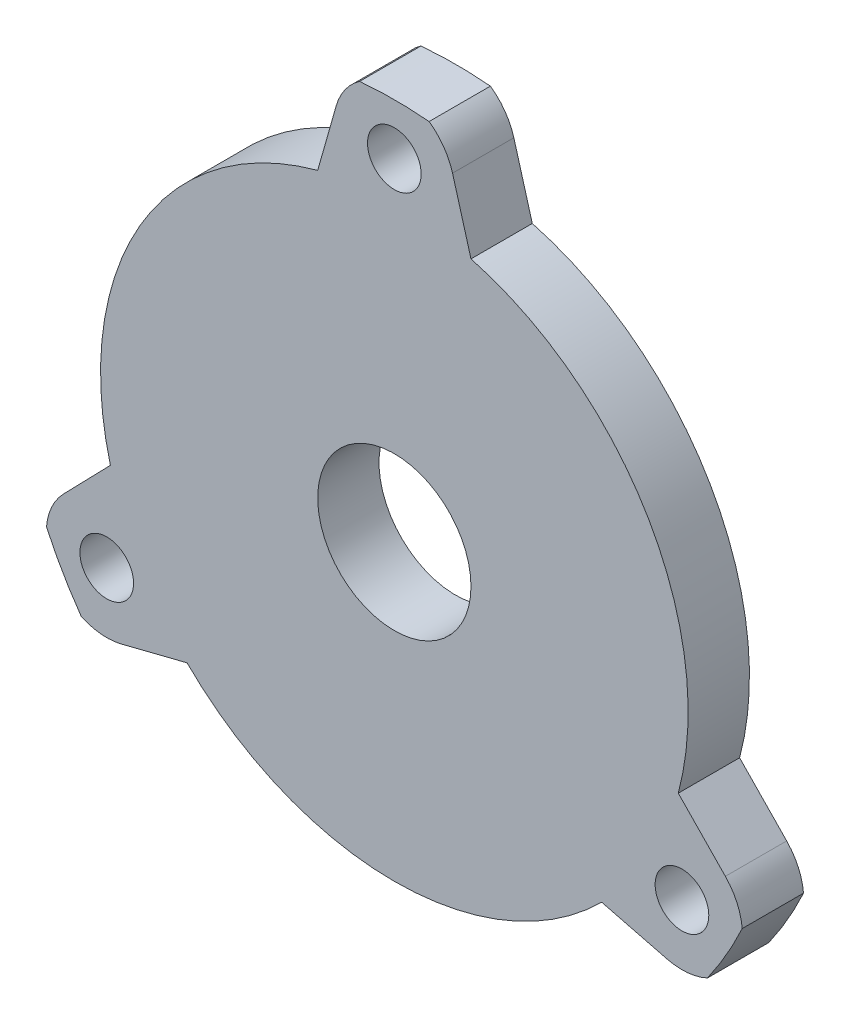
SolidWorks part; units mm, degrees
note: '?' marks a value the reader was unsure of.
material "AISI 1020"
ref_plane "Plano frontal" through (0, 0, 0) normal (0, 0, 1) x (1, 0, 0)
ref_plane "Plano superior" through (0, 0, 0) normal (0, 1, 0) x (1, 0, 0)
ref_plane "Plano direito" through (0, 0, 0) normal (1, 0, 0) x (0, 0, -1)
sketch "Esboço1" plane through (0, 0, 0) normal (0, 0, 1) x (1, 0, 0)
  circle A0 centre (0, 0) radius 75
  circle A1 centre (0, 0) radius 15
  dimension "D1" = 150
  dimension "D2" = 30
extrude "Extrusão1" add sketch "Esboço1" along normal mid plane 12
sketch "Esboço2" plane through (0, 0, 6) normal (0, 0, 1) x (1, 0, 0)
  circle A0 centre (0, 65) radius 5.25
  dimension "D1" = 10.5
  dimension "D2" = 65
extrude "Corte-extrusão1" cut sketch "Esboço2" against normal through all
ref_axis "Eixo1" through (0, 0, 6) along (0, 0, -1)?
pattern_circular "CirPattern1" count 3 over 360 about axis through (0, 0, 0) along (0, 0, 1) of "Corte-extrusão1"
sketch "Esboço3" plane through (0, 0, 6) normal (0, 0, 1) x (1, 0, 0)
  line L0 (11.3898, 68.2319) -> (15, 55.509)
  line L1 (0, 65) -> (0, 0) construction
  line L2 (-11.3898, 68.2319) -> (-15, 55.509)
  line L3 (53.3957, -43.9798) -> (40.5722, -40.7449)
  line L4 (64.7855, -24.2521) -> (55.5722, -14.7641)
  line L5 (-64.7855, -24.2521) -> (-55.5722, -14.7641)
  line L6 (-53.3957, -43.9798) -> (-40.5722, -40.7449)
  circle A0 centre (0, 0) radius 57.5
  circle A1 centre (0, 65) radius 11.8394
  circle A3 centre (56.2917, -32.5) radius 11.8394
  circle A4 centre (-56.2917, -32.5) radius 11.8394
  circle A5 centre (0, 0) radius 94.651
  circle M4 centre (0, 0) radius 75
  dimension "D1" = 115
  dimension "D2" = 30
extrude "Corte-extrusão3" cut sketch "Esboço3" against normal through all contours A5 M4 | A4 L5 A0 L2 A1 M4 | A4 A3 L3 A0 L6 M4 | A3 A1 L0 A0 L4 M4
